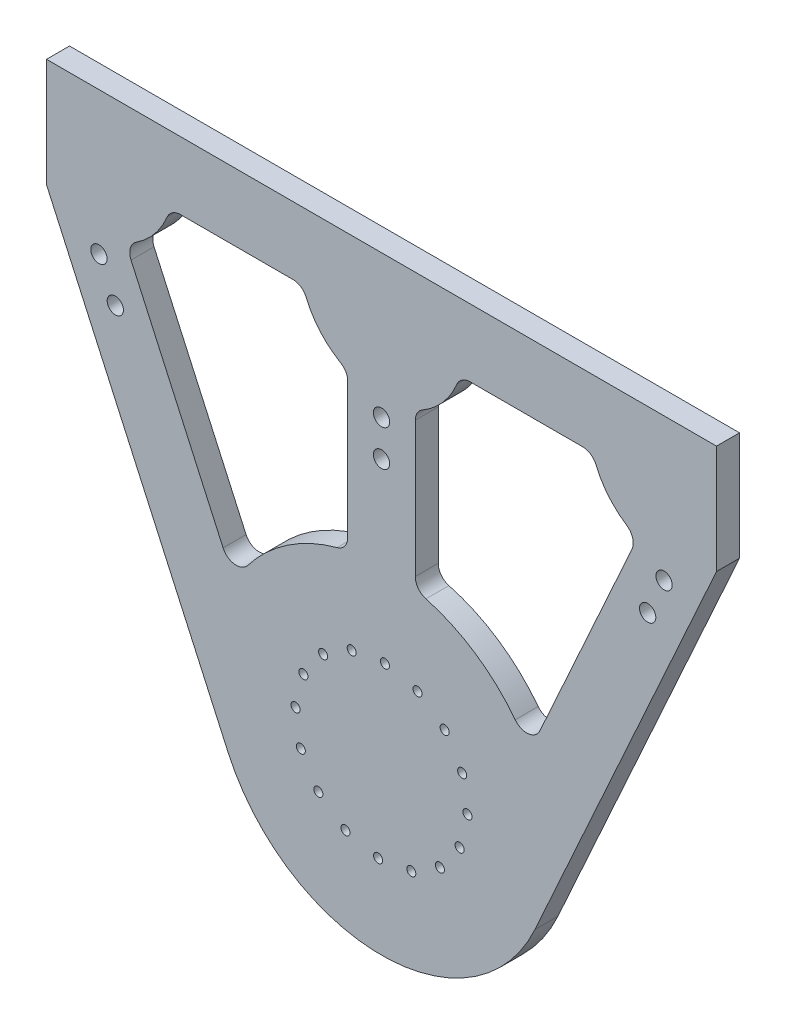
SolidWorks part; units mm, degrees
ref_plane "Front Plane" through (0, 0, 0) normal (0, 0, 1) x (1, 0, 0)
ref_plane "Top Plane" through (0, 0, 0) normal (0, 1, 0) x (1, 0, 0)
ref_plane "Right Plane" through (0, 0, 0) normal (1, 0, 0) x (0, 0, -1)
sketch "Sketch1" plane through (0, 0, 0) normal (0, 0, 1) x (1, 0, 0)
  line L1 (92.5, 121.5) -> (-92.5, 121.5)
  line L3 (0, 0) -> (0, 121.5) construction
  line L4 (-92.5, 121.5) -> (-92.5, 91.5)
  line L5 (-92.5, 91.5) -> (-42.3564, -19.1882)
  line L6 (92.5, 121.5) -> (92.5, 91.5)
  line L7 (92.5, 91.5) -> (42.3564, -19.1882)
  line L8 (42.3564, -19.1882) -> (-42.3564, -19.1882) construction
  circle A0 centre (0, 0) radius 46.5 construction
  arc A1 (-42.3564, -19.1882) -> (42.3564, -19.1882) centre (0, 0) ccw
  dimension "D1" = 93
  dimension "D2" = 185
  dimension "D3" = 121.5
  dimension "D4" = 30
extrude "Boss-Extrude1" add sketch "Sketch1" along normal mid plane 6.35
sketch "Sketch3" plane through (0, 0, -3.175) normal (0, 0, -1) x (-1, 0, 0)
  circle A0 centre (17.4402, -16.1215) radius 1.25 construction
  circle A1 centre (22.282, -8.2203) radius 1.25 construction
  circle A2 centre (9.9432, -21.5684) radius 1.25 construction
  circle A3 centre (0.9324, -23.7317) radius 1.25 construction
  circle A4 centre (-8.2203, -22.282) radius 1.25 construction
  circle A5 centre (-16.1215, -17.4402) radius 1.25 construction
  circle A6 centre (-21.5684, -9.9432) radius 1.25 construction
  circle A7 centre (-23.7317, -0.9324) radius 1.25 construction
  circle A8 centre (-22.282, 8.2203) radius 1.25 construction
  circle A9 centre (-17.4402, 16.1215) radius 1.25 construction
  circle A10 centre (-9.9432, 21.5684) radius 1.25 construction
  circle A11 centre (-0.9324, 23.7317) radius 1.25 construction
  circle A12 centre (8.2203, 22.282) radius 1.25 construction
  circle A13 centre (16.1215, 17.4402) radius 1.25 construction
  circle A14 centre (21.5684, 9.9432) radius 1.25 construction
  circle A15 centre (23.7317, 0.9324) radius 1.25 construction
  circle A16 centre (17.4402, -16.1215) radius 1.25
  circle A17 centre (22.282, -8.2203) radius 1.25
  circle A18 centre (9.9432, -21.5684) radius 1.25
  circle A19 centre (0.9324, -23.7317) radius 1.25
  circle A20 centre (-8.2203, -22.282) radius 1.25
  circle A21 centre (-16.1215, -17.4402) radius 1.25
  circle A22 centre (-21.5684, -9.9432) radius 1.25
  circle A23 centre (-23.7317, -0.9324) radius 1.25
  circle A24 centre (-22.282, 8.2203) radius 1.25
  circle A25 centre (-17.4402, 16.1215) radius 1.25
  circle A26 centre (-9.9432, 21.5684) radius 1.25
  circle A27 centre (-0.9324, 23.7317) radius 1.25
  circle A28 centre (8.2203, 22.282) radius 1.25
  circle A29 centre (16.1215, 17.4402) radius 1.25
  circle A30 centre (21.5684, 9.9432) radius 1.25
  circle A31 centre (23.7317, 0.9324) radius 1.25
extrude "Cut-Extrude2" cut sketch "Sketch3" against normal through all both and the other way through all
ref_plane "Plane1" through (0, 91.5, 0) normal (0, 1, 0) x (1, 0, 0)
ref_plane "Plane2" through (0, 106.5, 0) normal (0, 1, 0) x (1, 0, 0)
sketch "Sketch6" plane through (0, 0, -3.175) normal (0, 0, -1) x (-1, 0, 0)
  line L0 (0, 0) -> (0, 121.5) construction
  line L1 (-92.5, 121.5) -> (-77.5, 121.5) construction
  line L2 (-92.5, 121.5) -> (-92.5, 91.5) construction
  line L3 (-92.5, 91.5) -> (-77.5, 91.5) construction
  line L4 (-77.5, 121.5) -> (-77.5, 91.5) construction
  line L5 (-92.5, 121.5) -> (92.5, 121.5) construction
  line L6 (-85, 121.5) -> (-85, 106.5) construction
  line L11 (-77.5, 106.5) -> (-92.5, 106.5) construction
  line L12 (-7.5, 121.5) -> (7.5, 121.5) construction
  line L13 (-7.5, 121.5) -> (-7.5, 91.5) construction
  line L14 (-7.5, 91.5) -> (7.5, 91.5) construction
  line L15 (7.5, 121.5) -> (7.5, 91.5) construction
  line L16 (-85, 91.5) -> (-85, 106.5) construction
  circle A0 centre (-85, 114) radius 2.25
  circle A1 centre (-85, 99) radius 2.25
  circle A2 centre (0, 114) radius 2.25
  circle A3 centre (0, 99) radius 2.25
  circle A6 centre (85, 114) radius 2.25
  circle A7 centre (85, 99) radius 2.25
  point P18 (0, 121.5)
  point P35 (-85, 114)
  point P38 (-85, 99)
  dimension "D3" = 4.5
  dimension "D1" = 30
  dimension "D2" = 15
sketch "Sketch12" plane through (0, 0, -3.175) normal (0, 0, -1) x (-1, 0, 0)
  line L0 (0, -46.5) -> (0, 121.5) construction
  line L1 (-92.5, 121.5) -> (92.5, 121.5) construction
  line L2 (-87, 116) -> (-92.5, 116) construction
  line L3 (-87, 116) -> (-73, 116) construction
  line L4 (-87, 116) -> (-87, 102) construction
  line L5 (-87, 102) -> (-73, 102) construction
  line L6 (-73, 116) -> (-73, 102) construction
  line L7 (-92.5, 91.5) -> (-92.5, 121.5) construction
  line L8 (-87, 116) -> (-87, 121.5) construction
  line L9 (12.5, 121.5) -> (-12.5, 121.5) construction
  line L11 (-7, 102) -> (7, 102) construction
  line L12 (-7, 102) -> (-7, 116) construction
  line L13 (-7, 116) -> (7, 116) construction
  line L14 (7, 102) -> (7, 116) construction
  circle A0 centre (-7, 102) radius 2.25
  circle A2 centre (7, 102) radius 2.25
  circle A4 centre (7, 116) radius 2.25
  circle A5 centre (-87, 116) radius 2.25
  circle A6 centre (-73, 116) radius 2.25
  circle A7 centre (-73, 102) radius 2.25
  circle A8 centre (-87, 102) radius 2.25
  arc A9 (-42.3564, -19.1882) -> (42.3564, -19.1882) centre (0, 0) ccw construction
  circle A10 centre (87, 102) radius 2.25
  circle A11 centre (73, 102) radius 2.25
  circle A12 centre (73, 116) radius 2.25
  circle A13 centre (87, 116) radius 2.25
  circle A14 centre (-7, 116) radius 2.25
  point P22 (-87, 109)
  point P23 (-7, 109)
  point P24 (0, 116)
  dimension "D3" = 4.5
  dimension "D1" = 5.5
  dimension "D2" = 14
extrude "Cut-Extrude6" cut sketch "Sketch12" against normal through all both and the other way through all
sketch "Sketch13" plane through (0, 0, -3.175) normal (0, 0, -1) x (-1, 0, 0)
  line L0 (-40.7392, 22.418) -> (-70.6842, 88.5191)
  line L1 (40.7392, 22.418) -> (70.6842, 88.5191)
  line L2 (-9.3209, 88.5215) -> (-9.3209, 45.5562)
  line L3 (9.3209, 88.5215) -> (9.3209, 45.5562)
  line L7 (-7, 102) -> (7, 116) construction
  line L8 (-87, 102) -> (-73, 116) construction
  line L9 (58.3545, 102.8582) -> (21.6455, 102.8582)
  line L10 (-58.3545, 102.8582) -> (-21.6455, 102.8582)
  line L11 (25.3758, -11.4957) -> (73.8582, 95.5256)
  line L12 (73.8582, 95.5256) -> (73.8582, 102.8582)
  line L13 (73.8582, 102.8582) -> (-73.8582, 102.8582)
  line L14 (-73.8582, 102.8582) -> (-73.8582, 95.5256)
  line L15 (-73.8582, 95.5256) -> (-25.3758, -11.4957)
  line L16 (25.3758, -11.4957) -> (73.8582, 95.5256) construction
  line L17 (73.8582, 95.5256) -> (73.8582, 102.8582) construction
  line L18 (73.8582, 102.8582) -> (-73.8582, 102.8582) construction
  line L19 (-73.8582, 102.8582) -> (-73.8582, 95.5256) construction
  line L20 (-73.8582, 95.5256) -> (-25.3758, -11.4957) construction
  line L23 (0, 0) -> (0, 109) construction
  arc A0 (-40.7392, 22.418) -> (40.7392, 22.418) centre (0, 0) cw construction
  circle A1 centre (0, 0) radius 27.8582 construction
  arc A2 (-25.3758, -11.4957) -> (25.3758, -11.4957) centre (0, 0) ccw
  arc A3 (-25.3758, -11.4957) -> (25.3758, -11.4957) centre (0, 0) ccw construction
  circle A4 centre (7, 116) radius 2.25 construction
  circle A5 centre (-7, 102) radius 2.25 construction
  circle A6 centre (-73, 116) radius 2.25 construction
  circle A7 centre (-87, 102) radius 2.25 construction
  circle A8 centre (7, 116) radius 2.25 construction
  circle A9 centre (-7, 102) radius 2.25 construction
  circle A10 centre (-73, 116) radius 2.25 construction
  circle A11 centre (-87, 102) radius 2.25 construction
  circle A12 centre (-80, 109) radius 22.5 construction
  circle A13 centre (0, 109) radius 22.5 construction
  circle A14 centre (80, 109) radius 22.5 construction
  arc A15 (-70.6842, 88.5191) -> (-58.3545, 102.8582) centre (-80, 109) ccw
  arc A17 (58.3545, 102.8582) -> (70.6842, 88.5191) centre (80, 109) ccw
  arc A21 (-21.6455, 102.8582) -> (-9.3209, 88.5215) centre (0, 109) ccw
  arc A22 (9.3209, 88.5215) -> (21.6455, 102.8582) centre (0, 109) ccw
  arc A23 (-40.7392, 22.418) -> (-9.3209, 45.5562) centre (0, 0) cw
  arc A24 (9.3209, 45.5562) -> (40.7392, 22.418) centre (0, 0) cw
  point P1 (0, 0)
  dimension "D2" = 45
  dimension "D3" = 18.6418
  dimension "D4" = 46.5
  dimension "D1" = 18.6418
extrude "Cut-Extrude7" cut sketch "Sketch13" against normal through all both and the other way through all
fillet "Fillet4" radius 4 12 edges at (9.3209, 88.5215, 0) (9.3209, 45.5562, 0) (40.7392, 22.418, 0) (-70.6842, 88.5191, 0) (-40.7392, 22.418, 0) (-9.3209, 45.5562, 0) (-9.3209, 88.5215, 0) (-21.6455, 102.8582, 0) (-58.3545, 102.8582, 0) (21.6455, 102.8582, 0) (58.3545, 102.8582, 0) (70.6842, 88.5191, 0)
sketch "Sketch16" plane through (0, 0, 3.175) normal (0, 0, 1) x (1, 0, 0)
  circle A0 centre (-87, 102) radius 2.25 construction
  circle A1 centre (-87, 116) radius 2.25 construction
  circle A2 centre (-73, 116) radius 2.25 construction
  circle A3 centre (-73, 102) radius 2.25 construction
  circle A4 centre (-7, 116) radius 2.25 construction
  circle A5 centre (7, 116) radius 2.25 construction
  circle A6 centre (-7, 102) radius 2.25 construction
  circle A7 centre (7, 102) radius 2.25 construction
  circle A8 centre (73, 102) radius 2.25 construction
  circle A9 centre (87, 102) radius 2.25 construction
  circle A10 centre (73, 116) radius 2.25 construction
  circle A11 centre (87, 116) radius 2.25 construction
  circle A12 centre (-87, 102) radius 2.25
  circle A13 centre (-87, 116) radius 2.25
  circle A14 centre (-73, 116) radius 2.25
  circle A15 centre (-73, 102) radius 2.25
  circle A16 centre (-7, 116) radius 2.25
  circle A17 centre (7, 116) radius 2.25
  circle A18 centre (-7, 102) radius 2.25
  circle A19 centre (7, 102) radius 2.25
  circle A20 centre (73, 102) radius 2.25
  circle A21 centre (87, 102) radius 2.25
  circle A22 centre (73, 116) radius 2.25
  circle A23 centre (87, 116) radius 2.25
extrude "Boss-Extrude2" add sketch "Sketch16" against normal up to surface (6.35 mm away) up to face at (-35.1048, 75.6796, -3.175)
sketch "Sketch17" plane through (0, 0, -3.175) normal (0, 0, -1) x (-1, 0, 0)
  line L0 (0, 82.133) -> (78.0239, 82.133) construction
  line L1 (78.0239, 82.133) -> (73.4937, 72.133) construction
  line L2 (86.1416, 77.4644) -> (69.161, 85.1569) construction
  line L3 (92.5, 91.5) -> (42.3564, -19.1882) construction
  line L4 (69.161, 85.1569) -> (43.7423, 29.047) construction
  line L5 (-9.3209, 72.133) -> (9.3209, 72.133) construction
  line L6 (-9.3209, 86.0914) -> (-9.3209, 48.7114) construction
  line L7 (9.3209, 48.7114) -> (9.3209, 86.0914) construction
  line L8 (0, 82.133) -> (0, 72.133) construction
  line L9 (-92.5, 121.5) -> (92.5, 121.5) construction
  circle A0 centre (78.0239, 82.133) radius 2.25
  circle A1 centre (73.4937, 72.133) radius 2.25
  circle A2 centre (0, 82.133) radius 2.25
  circle A3 centre (0, 72.133) radius 2.25
  circle A4 centre (-73.4937, 72.133) radius 2.25
  circle A5 centre (-78.0239, 82.133) radius 2.25
  point P15 (0, 72.133)
  point P24 (77.6513, 81.3107)
  dimension "D1" = 4.5
  dimension "D2" = 10
  dimension "D3" = 39.367
extrude "Cut-Extrude8" cut sketch "Sketch17" against normal through all both and the other way through all
